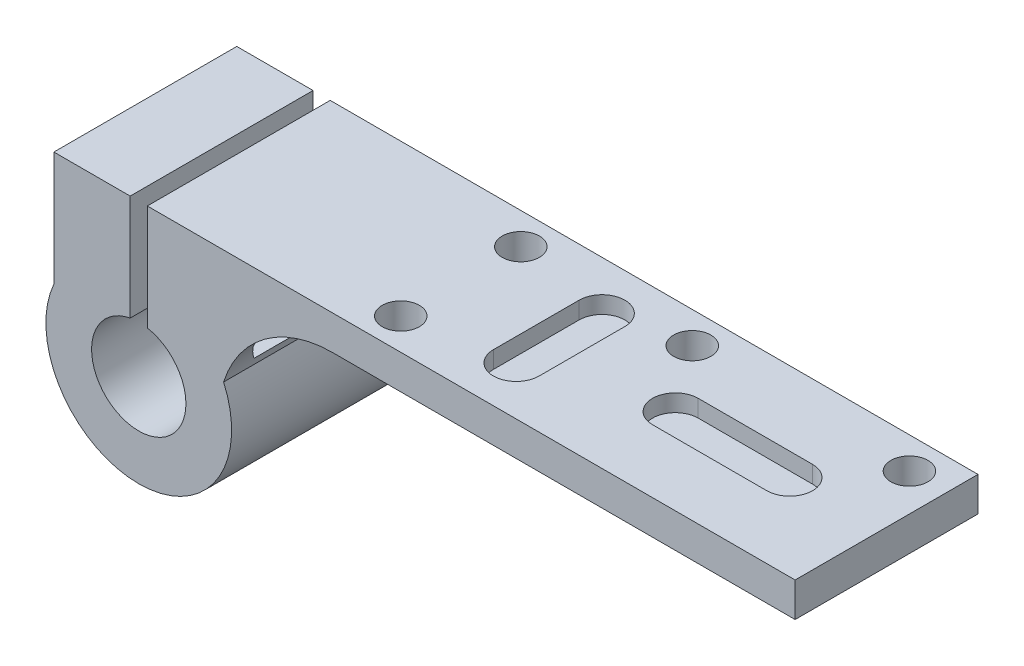
SolidWorks part; units mm, degrees
ref_plane "Front Plane" through (0, 0, 0) normal (0, 0, 1) x (1, 0, 0)
ref_plane "Top Plane" through (0, 0, 0) normal (0, 1, 0) x (1, 0, 0)
ref_plane "Right Plane" through (0, 0, 0) normal (1, 0, 0) x (0, 0, -1)
sketch "Sketch1" plane through (0, 0, 0) normal (0, 0, 1) x (1, 0, 0)
  line L1 (0.75, 13.3) -> (57.4246, 13.3)
  line L2 (57.4246, 13.3) -> (57.4246, 10.3)
  line L3 (57.4246, 10.3) -> (7.4247, 10.3)
  line L4 (7.4247, 10.3) -> (7.4247, 3.3)
  line L5 (-0.75, 4.0562) -> (-0.75, 13.3)
  line L7 (0.75, 4.0562) -> (0.75, 13.3)
  line L8 (-7.4247, 3.3) -> (-7.4247, 13.3)
  line L9 (-7.4247, 13.3) -> (-0.75, 13.3)
  arc A0 (-0.75, 4.0562) -> (0.75, 4.0562) centre (0, 0) ccw
  arc A2 (-7.4247, 3.3) -> (7.4247, 3.3) centre (0, 0) ccw
  dimension "D1" = 8.25
  dimension "D2" = 7
  dimension "D4" = 4
  dimension "D3" = 3
  dimension "D6" = 1.5
extrude "Boss-Extrude1" add sketch "Sketch1" along normal blind 16
sketch "Sketch2" plane through (0, 13.3, 0) normal (0, 1, 0) x (1, 0, 0)
  circle A0 centre (54.1746, -2.75) radius 1.625
  circle A1 centre (35.1746, -2.75) radius 1.625
  circle A2 centre (20.1746, -13.25) radius 1.625
  circle A3 centre (20.1746, -2.75) radius 1.625
  dimension "D1" = 3.25
extrude "Cut-Extrude1" cut sketch "Sketch2" against normal blind 10
sketch "Sketch3" plane through (7.4247, 0, 0) normal (1, 0, 0) x (0, 0, -1)
  line L0 (-16, 10.3) -> (0, 10.3) construction
  line L1 (0, 3.3) -> (0, 10.3) construction
  circle A0 centre (-4, 6.8) radius 1.625
  circle A1 centre (-12, 6.8) radius 1.625
  dimension "D1" = 3.25
  dimension "D3" = 8
  dimension "D2" = 3.5
  dimension "D4" = 4
extrude "Cut-Extrude2" cut sketch "Sketch3" against normal blind 19
sketch "Sketch4" plane through (7.4247, 0, 0) normal (1, 0, 0) x (0, 0, -1)
  line L1 (-8.7957, 6.8) -> (-10.3979, 9.575)
  line L2 (-10.3979, 9.575) -> (-13.6021, 9.575)
  line L3 (-13.6021, 9.575) -> (-15.2043, 6.8)
  line L4 (-15.2043, 6.8) -> (-13.6021, 4.025)
  line L5 (-13.6021, 4.025) -> (-10.3979, 4.025)
  line L6 (-10.3979, 4.025) -> (-8.7957, 6.8)
  line L7 (-0.6983, 6.8562) -> (-2.3005, 9.6312)
  line L8 (-2.3005, 9.6312) -> (-5.5048, 9.6312)
  line L9 (-5.5048, 9.6312) -> (-7.1069, 6.8562)
  line L10 (-7.1069, 6.8562) -> (-5.5048, 4.0812)
  line L11 (-5.5048, 4.0812) -> (-2.3005, 4.0812)
  line L12 (-2.3005, 4.0812) -> (-0.6983, 6.8562)
  circle A0 centre (-12, 6.8) radius 2.775 construction
  circle A1 centre (-3.9026, 6.8562) radius 2.775 construction
  dimension "D1" = 5.55
extrude "Cut-Extrude3" cut sketch "Sketch4" against normal blind 3
sketch "Sketch5" plane through (0, 13.3, 0) normal (0, 1, 0) x (1, 0, 0)
  line L0 (49.4246, -8.475) -> (39.4246, -8.475) construction
  line L1 (49.4246, -10.475) -> (39.4246, -10.475)
  line L2 (49.4246, -6.475) -> (39.4246, -6.475)
  line L3 (28.7746, -11.7444) -> (28.7746, -4.2444) construction
  line L4 (26.7746, -11.7444) -> (26.7746, -4.2444)
  line L5 (30.7746, -11.7444) -> (30.7746, -4.2444)
  arc A0 (49.4246, -10.475) -> (49.4246, -6.475) centre (49.4246, -8.475) ccw
  arc A1 (39.4246, -6.475) -> (39.4246, -10.475) centre (39.4246, -8.475) ccw
  arc A2 (26.7746, -11.7444) -> (30.7746, -11.7444) centre (28.7746, -11.7444) ccw
  arc A3 (30.7746, -4.2444) -> (26.7746, -4.2444) centre (28.7746, -4.2444) ccw
  point P2 (44.4246, -8.475)
  point P7 (28.7746, -7.9944)
  dimension "D1" = 2
extrude "Cut-Extrude4" cut sketch "Sketch5" against normal blind 1.5
fillet "Fillet1" radius 10 1 edges at (7.4247, 10.3, 8)
sketch "Sketch6" plane through (-7.4247, 0, 0) normal (-1, 0, 0) x (0, 0, 1)
  circle A0 centre (4, 6.8) radius 3
  circle A1 centre (12, 6.8) radius 3
  dimension "D1" = 6
extrude "Cut-Extrude5" cut sketch "Sketch6" against normal blind 3
